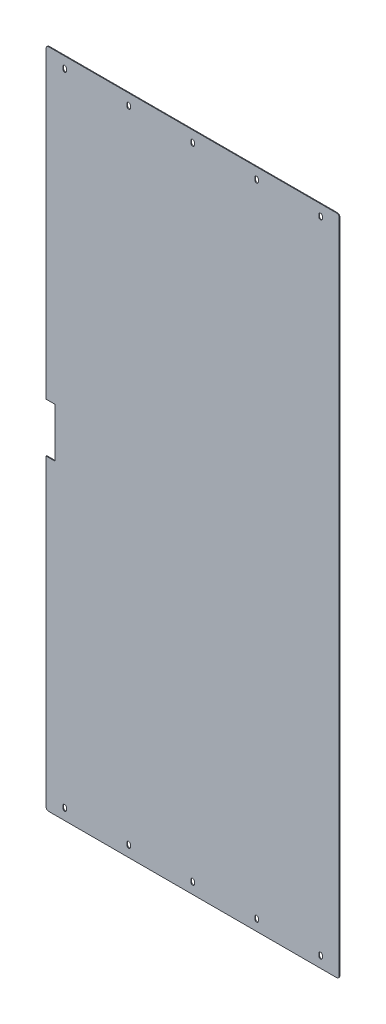
SolidWorks part; units mm, degrees
ref_plane "前视基准面" through (0, 0, 0) normal (0, 0, 1) x (1, 0, 0)
ref_plane "上视基准面" through (0, 0, 0) normal (0, 1, 0) x (1, 0, 0)
ref_plane "右视基准面" through (0, 0, 0) normal (1, 0, 0) x (0, 0, -1)
sketch "草图1" plane through (0, 0, 0) normal (0, 0, 1) x (1, 0, 0)
  line L1 (297.5, -672.5) -> (-297.5, -672.5)
  line L2 (297.5, -672.5) -> (297.5, 672.5)
  line L3 (297.5, 672.5) -> (-297.5, 672.5)
  line L4 (-297.5, -672.5) -> (-297.5, 672.5)
  line L5 (297.5, -672.5) -> (-297.5, 672.5) construction
  line L6 (297.5, 672.5) -> (-297.5, -672.5) construction
  point P0 (0, 0)
  dimension "D1" = 1345
  dimension "D2" = 595
base flange "基体-法兰1" sketch "草图1" thickness 1.5 reverse thickness direction no parameters "D1"=0.7366
fillet "圆角1" radius 5 4 edges at (297.5, 672.5, -0.75) (-297.5, 672.5, -0.75) (297.5, -672.5, -0.75) (-297.5, -672.5, -0.75)
sketch "草图2" plane through (0, 0, 0) normal (0, 0, 1) x (1, 0, 0)
  line L0 (-260, 647.5) -> (-260, 652.5) construction
  line L1 (-263.5, 647.5) -> (-263.5, 652.5)
  line L2 (-256.5, 647.5) -> (-256.5, 652.5)
  line L3 (292.5, 672.5) -> (-292.5, 672.5) construction
  line L4 (-297.5, 667.5) -> (-297.5, -667.5) construction
  line L5 (-260, -652.5) -> (-260, -647.5) construction
  line L6 (-263.5, -652.5) -> (-263.5, -647.5)
  line L7 (-256.5, -652.5) -> (-256.5, -647.5)
  line L8 (-292.5, -672.5) -> (292.5, -672.5) construction
  arc A0 (-263.5, 647.5) -> (-256.5, 647.5) centre (-260, 647.5) ccw
  arc A1 (-256.5, 652.5) -> (-263.5, 652.5) centre (-260, 652.5) ccw
  arc A2 (-263.5, -652.5) -> (-256.5, -652.5) centre (-260, -652.5) ccw
  arc A3 (-256.5, -647.5) -> (-263.5, -647.5) centre (-260, -647.5) ccw
  point P2 (-260, 650)
  point P13 (-260, -650)
  dimension "D1" = 7
  dimension "D2" = 5
  dimension "D3" = 22.5
  dimension "D4" = 37.5
  dimension "D5" = 7
  dimension "D6" = 5
  dimension "D7" = 22.5
extrude "切除-拉伸1" cut sketch "草图2" against normal blind 10 normal cut yes
pattern_linear "阵列(线性)1" count 5 spacing 130 along (1, 0, 0) of "切除-拉伸1"
sketch "草图3" plane through (0, 0, -1.5) normal (0, 0, -1) x (-1, 0, 0)
  line L0 (297.5, 667.5) -> (297.5, -667.5) construction
  line L1 (297.5, 50) -> (279.5, 50)
  line L2 (297.5, 50) -> (297.5, -50)
  line L3 (297.5, -50) -> (279.5, -50)
  line L4 (279.5, 50) -> (279.5, -50)
  dimension "D1" = 100
  dimension "D2" = 50
  dimension "D3" = 18
extrude "切除-拉伸2" cut sketch "草图3" against normal blind 10 normal cut yes
sketch "折弯-线1" [suppressed] plane through (0, 0, 0) normal (0, 1, 0) x (1, 0, 0)
sketch "边界框1" [suppressed] plane through (0, 0, 0) normal (0, 1, 0) x (1, 0, 0)
sheet metal parameters "钣金1" thickness 1.5 parameters "D1"=0.7366
flat pattern "平板型式1" [suppressed]
sketch "折弯-线2" plane through (0, 0, 0) normal (0, 1, 0) x (1, 0, 0)
sketch3d "边界框2" [suppressed]
  line L0 (297.4999, -672.5, 0) -> (297.5, 672.5, 0) construction
  line L1 (-297.5, -672.5, 0) -> (-297.4999, 672.5, 0) construction
  line L2 (297.4999, -672.5, 0) -> (-297.5, -672.5, 0) construction
  line L3 (297.5, 672.5, 0) -> (-297.4999, 672.5, 0) construction
sheet metal parameters "钣金2" thickness 1.5 parameters "D1"=0.7366
flat pattern "平板型式1"
sketch "折弯-线2" plane through (0, 0, 0) normal (0, 1, 0) x (1, 0, 0)
sketch3d "边界框2" [suppressed]
  line L0 (297.4999, -672.5, 0) -> (297.5, 672.5, 0) construction
  line L1 (-297.5, -672.5, 0) -> (-297.4999, 672.5, 0) construction
  line L2 (297.4999, -672.5, 0) -> (-297.5, -672.5, 0) construction
  line L3 (297.5, 672.5, 0) -> (-297.4999, 672.5, 0) construction
sheet metal parameters "钣金3" thickness 1.5 parameters "D1"=0.7366
flat pattern "平板型式1"
sketch "折弯-线2" plane through (0, 0, 0) normal (0, 1, 0) x (1, 0, 0)
sketch3d "边界框2" [suppressed]
  line L0 (297.4999, -672.5, 0) -> (297.5, 672.5, 0) construction
  line L1 (-297.5, -672.5, 0) -> (-297.4999, 672.5, 0) construction
  line L2 (297.4999, -672.5, 0) -> (-297.5, -672.5, 0) construction
  line L3 (297.5, 672.5, 0) -> (-297.4999, 672.5, 0) construction
sheet metal parameters "钣金4" thickness 1.5 parameters "D1"=0.7366
flat pattern "平板型式1"
sketch "折弯-线2" plane through (0, 0, 0) normal (0, 1, 0) x (1, 0, 0)
sketch3d "边界框2" [suppressed]
  line L0 (297.4999, -672.5, 0) -> (297.5, 672.5, 0) construction
  line L1 (-297.5, -672.5, 0) -> (-297.4999, 672.5, 0) construction
  line L2 (297.4999, -672.5, 0) -> (-297.5, -672.5, 0) construction
  line L3 (297.5, 672.5, 0) -> (-297.4999, 672.5, 0) construction
